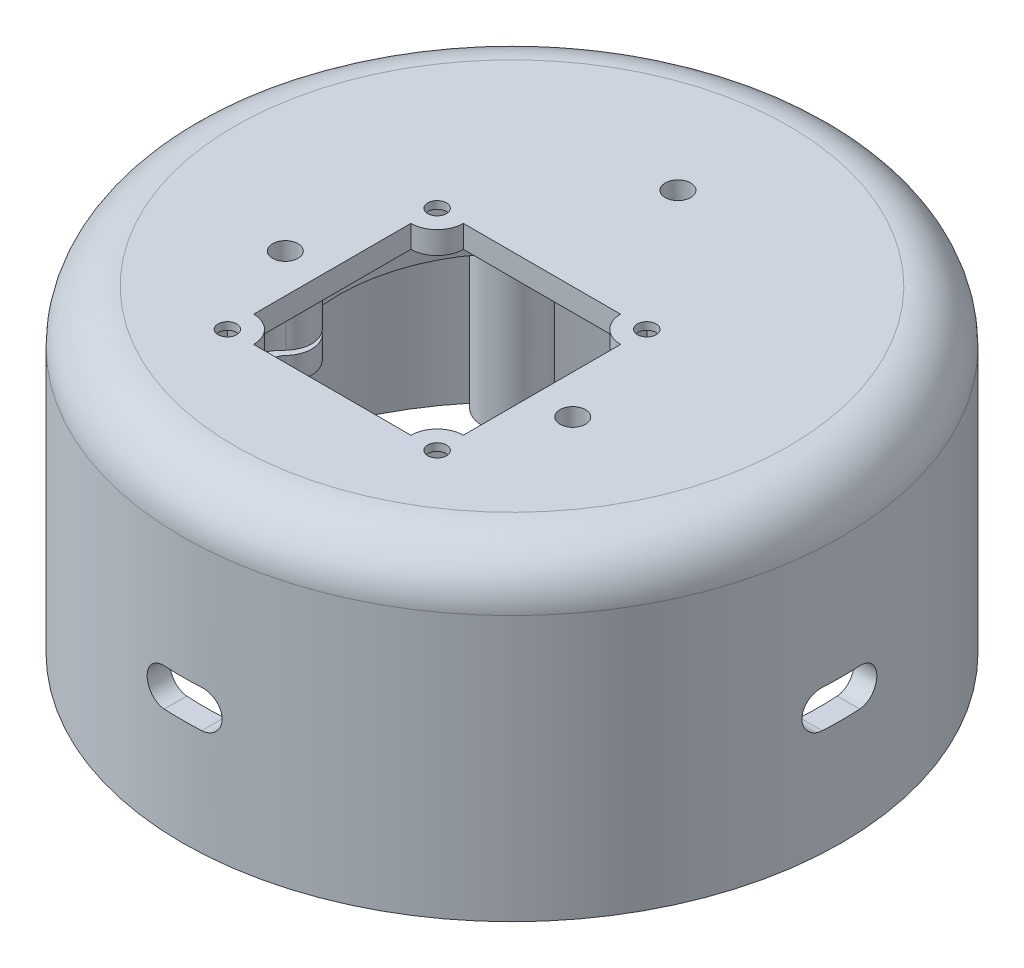
SolidWorks part; units mm, degrees
ref_plane "Plan de face" through (0, 0, 0) normal (0, 0, 1) x (1, 0, 0)
ref_plane "Plan de dessus" through (0, 0, 0) normal (0, 1, 0) x (1, 0, 0)
ref_plane "Plan de droite" through (0, 0, 0) normal (1, 0, 0) x (0, 0, -1)
sketch "Esquisse1" plane through (0, 0, 0) normal (0, 0, 1) x (1, 0, 0)
  line L0 (0, 0) -> (0, 42.4) construction
  line L1 (0, 42.4) -> (37, 42.4)
  line L2 (44, 35.4) -> (44, 0)
  line L3 (44, 0) -> (0, 0) construction
  line L4 (0, 39.4) -> (37, 39.4)
  line L5 (41, 35.4) -> (41, 0)
  line L6 (0, 42.4) -> (0, 39.4)
  line L7 (41, 0) -> (44, 0)
  arc A0 (37, 42.4) -> (44, 35.4) centre (37, 35.4) cw
  arc A1 (37, 39.4) -> (41, 35.4) centre (37, 35.4) cw
  dimension "D1" = 88
  dimension "D2" = 37
  dimension "D3" = 42.4
  dimension "D5" = 41
  dimension "D4" = 3
revolve "Révolution1" add sketch "Esquisse1" angle 360 about L0
sketch "Esquisse2" plane through (0, 0, 0) normal (0, -1, 0) x (1, 0, 0)
  line L0 (0, 0) -> (-28.2843, 28.2843) construction
  line L1 (0, 0) -> (0, 41) construction
  arc A0 (-26.0893, 31.6283) -> (-31.6283, 26.0893) centre (-28.2843, 28.2843) cw
  circle A1 centre (0, 0) radius 41 construction
  arc A2 (-31.6283, 26.0893) -> (-26.0893, 31.6283) centre (0, 0) cw
  dimension "D2" = 4
  dimension "D1" = 40
  dimension "D3" = 45
extrude "Boss.-Extru.1" add sketch "Esquisse2" against normal up to next
hole_wizard "Chambrage pour vis à tête hexagonale M51" positions "Esquisse3D1" profile "Esquisse4" counterbore size "M5" standard "Ansi Metric"
sketch3d "Esquisse3D1"
  point P0 (-28.2843, 0, 28.2843)
sketch "Esquisse4" plane through (-28.2843, 0, 28.2843) normal (1, 0, 0) x (0, 0, -1)
  line L0 (0, 0) -> (0, 16.0215)
  line L1 (0, 16.0215) -> (1.7, 15)
  line L2 (1.7, 15) -> (1.7, 4.8)
  line L3 (1.7, 4.8) -> (2.175, 4.8)
  line L4 (2.175, 4.8) -> (2.175, 0)
  line L5 (2.175, 0) -> (0, 0)
  line L10 (0, 16.0215) -> (-1.7, 15) construction
  line L11 (0, -6.35) -> (0, 107.95) construction
  dimension "Diamètre du perçage" = 3.4
  dimension "Profondeur du perçage" = 15
  dimension "Diamètre du chambrage" = 4.35
  dimension "Profondeur du chambrage" = 4.8
  dimension "Angle de pointe" = 118
pattern_circular "Répétition circulaire1" count 4 over 360 about axis through (0, 0, 0) along (0, 1, 0) of "Chambrage pour vis à tête hexagonale M51", "Boss.-Extru.1"
sketch "Esquisse5" plane through (0, 42.4, 0) normal (0, 1, 0) x (1, 0, 0)
  line L5 (-14, 4) -> (14, 4) construction
  line L6 (-14, 4) -> (-14, -24) construction
  line L7 (-14, -24) -> (14, -24) construction
  line L8 (14, 4) -> (14, -24) construction
  line L9 (0, -24) -> (0, 4) construction
  line L10 (-14, -10) -> (14, -10) construction
  circle A1 centre (-14, 4) radius 1.25
  circle A2 centre (14, 4) radius 1.25
  circle A3 centre (14, -24) radius 1.25
  circle A4 centre (-14, -24) radius 1.25
  point P192 (0, 0)
  dimension "D2" = 2.5
  dimension "D1" = 28
  dimension "D3" = 10
extrude "Enlèv. mat.-Extru.1" cut sketch "Esquisse5" against normal through all
sketch "Esquisse6" plane through (0, 42.4, 0) normal (0, 1, 0) x (1, 0, 0)
  line L0 (-14, 4) -> (-14, -24) construction
  line L1 (-14, -10) -> (-14, 0.5)
  line L2 (-10.5, 4) -> (0, 4)
  line L3 (14, 0.5) -> (14, -10)
  line L4 (0, 4) -> (10.5, 4)
  line L5 (10.5, -24) -> (0, -24)
  line L6 (14, -10) -> (14, -20.5)
  line L7 (-14, -20.5) -> (-14, -10)
  line L8 (0, -24) -> (-10.5, -24)
  line L9 (0, 4) -> (0, -10) construction
  line L10 (0, -10) -> (14, -10) construction
  arc A0 (-14, 0.5) -> (-10.5, 4) centre (-14, 4) ccw
  arc A1 (10.5, 4) -> (14, 0.5) centre (14, 4) ccw
  arc A2 (14, -20.5) -> (10.5, -24) centre (14, -24) ccw
  arc A3 (-10.5, -24) -> (-14, -20.5) centre (-14, -24) ccw
  point P27 (0, -10)
  dimension "D1" = 21
  dimension "D2" = 4
extrude "Enlèv. mat.-Extru.2" cut sketch "Esquisse6" against normal through all
sketch "Esquisse7" plane through (0, 39.4, 0) normal (0, -1, 0) x (1, 0, 0)
  line L0 (-12.4974, 22.4974) -> (0, 10) construction
  line L1 (-12.2649, 25.7351) -> (-14.6351, 26.3701)
  line L2 (-14.6351, 26.3701) -> (-16.3701, 24.6351)
  line L3 (-16.3701, 24.6351) -> (-15.7351, 22.2649)
  line L4 (-15.7351, 22.2649) -> (-13.3649, 21.6299)
  line L5 (-13.3649, 21.6299) -> (-11.6299, 23.3649)
  line L6 (-11.6299, 23.3649) -> (-12.2649, 25.7351)
  line L7 (15.7351, 22.2649) -> (16.3701, 24.6351)
  line L8 (16.3701, 24.6351) -> (14.6351, 26.3701)
  line L9 (14.6351, 26.3701) -> (12.2649, 25.7351)
  line L10 (12.2649, 25.7351) -> (11.6299, 23.3649)
  line L11 (11.6299, 23.3649) -> (13.3649, 21.6299)
  line L12 (13.3649, 21.6299) -> (15.7351, 22.2649)
  line L13 (12.2649, -5.7351) -> (14.6351, -6.3701)
  line L14 (14.6351, -6.3701) -> (16.3701, -4.6351)
  line L15 (16.3701, -4.6351) -> (15.7351, -2.2649)
  line L16 (15.7351, -2.2649) -> (13.3649, -1.6299)
  line L17 (13.3649, -1.6299) -> (11.6299, -3.3649)
  line L18 (11.6299, -3.3649) -> (12.2649, -5.7351)
  line L19 (-15.7351, -2.2649) -> (-16.3701, -4.6351)
  line L20 (-16.3701, -4.6351) -> (-14.6351, -6.3701)
  line L21 (-14.6351, -6.3701) -> (-12.2649, -5.7351)
  line L22 (-12.2649, -5.7351) -> (-11.6299, -3.3649)
  line L23 (-11.6299, -3.3649) -> (-13.3649, -1.6299)
  line L24 (-13.3649, -1.6299) -> (-15.7351, -2.2649)
  line L25 (0, 24) -> (0, -4) construction
  line L26 (10.5, 24) -> (-10.5, 24) construction
  line L27 (-10.5, -4) -> (10.5, -4) construction
  circle A0 centre (-14, 24) radius 2.125 construction
  point P10 (13.3671, 21.8695)
  point P22 (11.8695, -3.3671)
  point P29 (-13.3671, -1.8695)
  point P36 (-11.8695, 23.3671)
  point P37 (0, 10)
  dimension "D1" = 4.25
  dimension "D2" = 4
extrude "Enlèv. mat.-Extru.3" cut sketch "Esquisse7" against normal blind 2
sketch "Esquisse8" plane through (0, 39.4, 0) normal (0, -1, 0) x (1, 0, 0)
  circle A0 centre (0, 0) radius 32.77
  circle A1 centre (0, 0) radius 26.16
  dimension "D1" = 65.54
  dimension "D2" = 52.32
extrude "Boss.-Extru.2" add sketch "Esquisse8" along normal blind 1.6 from offset 5 separate body
sketch "Esquisse9" plane through (0, 39.4, 0) normal (0, -1, 0) x (1, 0, 0)
  circle A0 centre (0, 0) radius 32.77 construction
  circle A1 centre (0, 0) radius 26.16 construction
  circle A2 centre (0, 0) radius 32.77 construction
  circle A3 centre (0, 0) radius 26.16 construction
  circle A4 centre (0, 0) radius 25.66
  circle A5 centre (0, 0) radius 33.27
  dimension "D1" = 0.5
  dimension "D2" = 0.5
extrude "Boss.-Extru.3" add sketch "Esquisse9" along normal up to surface (5 mm away) up to face at (0, 34.4, -32.77)
sketch "Esquisse10" plane through (0, 34.4, 0) normal (0, -1, 0) x (1, 0, 0)
  line L0 (-25.019, 21.9305) -> (-19.2963, 16.9142)
  line L1 (25.019, 21.9305) -> (19.2963, 16.9142)
  line L2 (-19.2963, 16.9142) -> (19.2963, 16.9142) construction
  line L3 (0, 16.9142) -> (0, 0) construction
  line L4 (6.4829, -32.6323) -> (5, -25.1681)
  line L5 (31.5018, 10.7018) -> (24.2963, 8.2539)
  line L6 (-31.5018, 10.7018) -> (-24.2963, 8.2539)
  line L7 (-6.4829, -32.6323) -> (-5, -25.1681)
  circle A0 centre (0, 0) radius 33.27 construction
  circle A1 centre (0, 0) radius 25.66 construction
  arc A2 (-25.019, 21.9305) -> (25.019, 21.9305) centre (0, 0) cw
  arc A3 (-19.2963, 16.9142) -> (19.2963, 16.9142) centre (0, 0) cw
  arc A4 (24.2963, 8.2539) -> (5, -25.1681) centre (0, 0) cw
  arc A5 (31.5018, 10.7018) -> (6.4829, -32.6323) centre (0, 0) cw
  arc A6 (-5, -25.1681) -> (-24.2963, 8.2539) centre (0, 0) cw
  arc A7 (-6.4829, -32.6323) -> (-31.5018, 10.7018) centre (0, 0) cw
  point P8 (0, 0)
  point P26 (0, 0)
  dimension "D1" = 3
  dimension "D2" = 10
extrude "Enlèv. mat.-Extru.4" cut sketch "Esquisse10" against normal up to surface (5 mm away) up to face at (0, 39.4, -33.27)
sketch "Esquisse11" plane through (0, 39.4, 0) normal (0, -1, 0) x (1, 0, 0)
  line L0 (-5, -25.1681) -> (-4.8051, -24.1873)
  line L1 (5, -25.1681) -> (4.8051, -24.1873)
  line L2 (-6.4829, -32.6323) -> (-6.6777, -33.6131)
  line L3 (6.4829, -32.6323) -> (6.6777, -33.6131)
  arc A0 (-6.4829, -32.6323) -> (6.4829, -32.6323) centre (0, 0) ccw construction
  arc A1 (-5, -25.1681) -> (5, -25.1681) centre (0, 0) ccw construction
  arc A2 (-6.4829, -32.6323) -> (6.4829, -32.6323) centre (0, 0) ccw
  arc A3 (-5, -25.1681) -> (5, -25.1681) centre (0, 0) ccw
  arc A4 (-4.8051, -24.1873) -> (4.8051, -24.1873) centre (0, 0) ccw
  arc A5 (-6.6777, -33.6131) -> (6.6777, -33.6131) centre (0, 0) ccw
  dimension "D1" = 1
  dimension "D2" = 1
extrude "Boss.-Extru.4" add sketch "Esquisse11" along normal offset from surface (6 mm away) 1 up to face at (0, 34.4, -29.1826) offset beyond the face yes
pattern_circular "Répétition circulaire2" count 3 over 360 about axis through (0, 0, 0) along (0, 1, 0) of "Boss.-Extru.4"
sketch "Esquisse13" plane through (0, 39.4, 0) normal (0, -1, 0) x (1, 0, 0)
  line L0 (0, 36) -> (0, 24) construction
  line L1 (10.5, 24) -> (-10.5, 24) construction
  circle A2 centre (0, 30) radius 1
  dimension "D1" = 2
sketch "Esquisse15" plane through (0, 0, 0) normal (0, -1, 0) x (1, 0, 0)
  line L0 (-28.2843, 28.2843) -> (28.2843, 28.2843) construction
  line L1 (0, 28.2843) -> (0, 44) construction
  circle A0 centre (0, 0) radius 44 construction
ref_plane "Plan1" through (0, 0, 0) normal (1, 0, 0) x (0, 0, 1)
sketch "Esquisse16" plane through (0, 0, 0) normal (1, 0, 0) x (0, 0, 1)
  line L0 (21.9305, -33.4) -> (10.7018, -33.4) construction
  line L1 (21.9305, -33.4) -> (10.7018, -33.4) construction
  line L2 (-2.5, -16.7) -> (2.5, -16.7) construction
  line L3 (-2.5, -14.2) -> (2.5, -14.2)
  line L4 (-2.5, -19.2) -> (2.5, -19.2)
  line L5 (0, 0) -> (0, -33.4) construction
  line L6 (26.0893, 0) -> (-26.0893, 0) construction
  line L7 (0, -33.4) -> (21.9305, -33.4) construction
  arc A0 (-2.5, -14.2) -> (-2.5, -19.2) centre (-2.5, -16.7) ccw
  arc A1 (2.5, -19.2) -> (2.5, -14.2) centre (2.5, -16.7) ccw
  point P4 (0, -16.7)
  dimension "D1" = 5
  dimension "D2" = 5
extrude "Enlèv. mat.-Extru.7" cut sketch "Esquisse16" against normal through all
pattern_circular "Répétition circulaire3" count 4 over 360 about axis through (0, 0, 0) along (0, -1, 0) of "Enlèv. mat.-Extru.7"
sketch "Esquisse17" plane through (0, 39.4, 0) normal (0, -1, 0) x (1, 0, 0)
  line L0 (-21.3562, 12.33) -> (-19.1911, 11.08) construction
  line L1 (-21.3562, 12.33) -> (-17.3021, 19.352) construction
  arc A0 (-18.5443, 16.255) -> (-23.3494, 7.9323) centre (0, 0) ccw construction
  circle A1 centre (-19.1911, 11.08) radius 3.5
  arc A2 (-18.5443, 16.255) -> (-23.3494, 7.9323) centre (0, 0) ccw
  dimension "D1" = 7
  dimension "D2" = 2.5
extrude "Boss.-Extru.5" add sketch "Esquisse17" along normal up to surface (6 mm away) contours A1 A2 up to face at (-21.5804, 33.4, 12.4594)
hole_wizard "Chambrage pour vis à tête hexagonale M52" positions "Esquisse3D2" profile "Esquisse18" counterbore size "M5" standard "Ansi Metric"
sketch3d "Esquisse3D2"
  line L0 (-19.1911, 33.4, 11.08) -> (-19.1911, 39.4, 11.08) construction
  point P0 (-19.1911, 33.4, 11.08)
sketch "Esquisse18" plane through (-19.1911, 33.4, 11.08) normal (1, 0, 0) x (0, 0, -1)
  line L0 (0, 0) -> (0, 11.0215)
  line L1 (0, 11.0215) -> (1.7, 10)
  line L2 (1.7, 10) -> (1.7, 4.8)
  line L3 (1.7, 4.8) -> (2.175, 4.8)
  line L4 (2.175, 4.8) -> (2.175, 0)
  line L5 (2.175, 0) -> (0, 0)
  line L10 (0, 11.0215) -> (-1.7, 10) construction
  line L11 (0, -6.35) -> (0, 107.95) construction
  dimension "Diamètre du perçage" = 3.4
  dimension "Profondeur du perçage" = 10
  dimension "Diamètre du chambrage" = 4.35
  dimension "Profondeur du chambrage" = 4.8
  dimension "Angle de pointe" = 118
pattern_circular "Répétition circulaire10" count 3 over 360 about axis through (0, 0, 0) along (0, 1, 0) of "Boss.-Extru.5", "Chambrage pour vis à tête hexagonale M52"
fillet "Congé1" radius 10 6 edges at (-22.5292, 36.4, 10.0276) (-19.9487, 36.4, 14.497) (2.5804, 36.4, -24.5246) (-2.5804, 36.4, -24.5246) (19.9487, 36.4, 14.497) (22.5292, 36.4, 10.0276)
sketch "Esquisse19" plane through (0, 33.4, 0) normal (0, -1, 0) x (1, 0, 0)
  line L0 (-19.1911, 11.08) -> (-20.0571, 11.58) construction
  circle A0 centre (0, 0) radius 34.27
  arc A1 (-25.771, 22.5896) -> (-32.4487, 11.0235) centre (0, 0) ccw construction
  circle A2 centre (0, -22.16) radius 1.7 construction
  circle A3 centre (19.1911, 11.08) radius 1.7 construction
  circle A4 centre (-19.1911, 11.08) radius 1.7 construction
  circle A5 centre (0, -22.16) radius 1.7
  circle A6 centre (19.1911, 11.08) radius 1.7
  circle A7 centre (-19.1911, 11.08) radius 1.7
  arc A8 (-20.0311, 7.6823) -> (-16.6686, 13.5063) centre (-19.1911, 11.08) ccw construction
  arc A9 (-20.0311, 7.6823) -> (-16.6686, 13.5063) centre (-19.1911, 11.08) ccw
  arc A10 (-20.0311, 7.6823) -> (-22.2602, 6.393) centre (-20.4765, 5.8807) ccw
  arc A11 (20.0311, 7.6823) -> (22.2602, 6.393) centre (20.4765, 5.8807) cw
  arc A12 (-16.6686, 13.5063) -> (-16.6666, 16.0814) centre (-15.3311, 14.7928) cw
  circle A13 centre (0, 0) radius 23.16
  circle A14 centre (0, 0) radius 23.16 construction
  arc A15 (16.6686, 13.5063) -> (20.0311, 7.6823) centre (19.1911, 11.08) ccw
  arc A16 (16.6686, 13.5063) -> (16.6666, 16.0814) centre (15.3311, 14.7928) ccw
  arc A17 (-3.3625, -21.1886) -> (-5.5936, -22.4744) centre (-5.1454, -20.6735) cw
  arc A18 (3.3625, -21.1886) -> (-3.3625, -21.1886) centre (0, -22.16) ccw
  arc A19 (3.3625, -21.1886) -> (5.5936, -22.4744) centre (5.1454, -20.6735) ccw
  arc A20 (-22.2602, 6.393) -> (-5.5936, -22.4744) centre (0, 0) ccw
  arc A21 (5.5936, -22.4744) -> (22.2602, 6.393) centre (0, 0) ccw
  arc A22 (-16.6666, 16.0814) -> (16.6666, 16.0814) centre (0, 0) cw
  point P42 (0, 0)
  circle M17 centre (19.1911, 11.08) radius 2.175
  line M18 (23.3494, 7.9323) -> (24.2963, 8.2539)
  arc M19 (24.2963, 8.2539) -> (19.2963, 16.9142) centre (0, 0) ccw
  line M20 (19.2963, 16.9142) -> (18.5443, 16.255)
  arc M21 (18.5443, 16.255) -> (16.6686, 13.5063) centre (9.4614, 20.4386) cw
  arc M22 (16.6686, 13.5063) -> (20.0311, 7.6823) centre (19.1911, 11.08) ccw
  arc M23 (20.0311, 7.6823) -> (23.3494, 7.9323) centre (22.431, -2.0255) cw
  dimension "D1" = 3
  dimension "D2" = 3
extrude "Boss.-Extru.6" add sketch "Esquisse19" along normal blind 3 from surface at 0.6 separate body contours A0 A7 A5 A12 A22 A16 A11 A21 A19 A18 A17 A20 A10 A9 M21 M20 M19 M18 M23 | M23 M18 M19 M20 M21 M22 M17 starting at face at (0, 32.8, -32.77)
